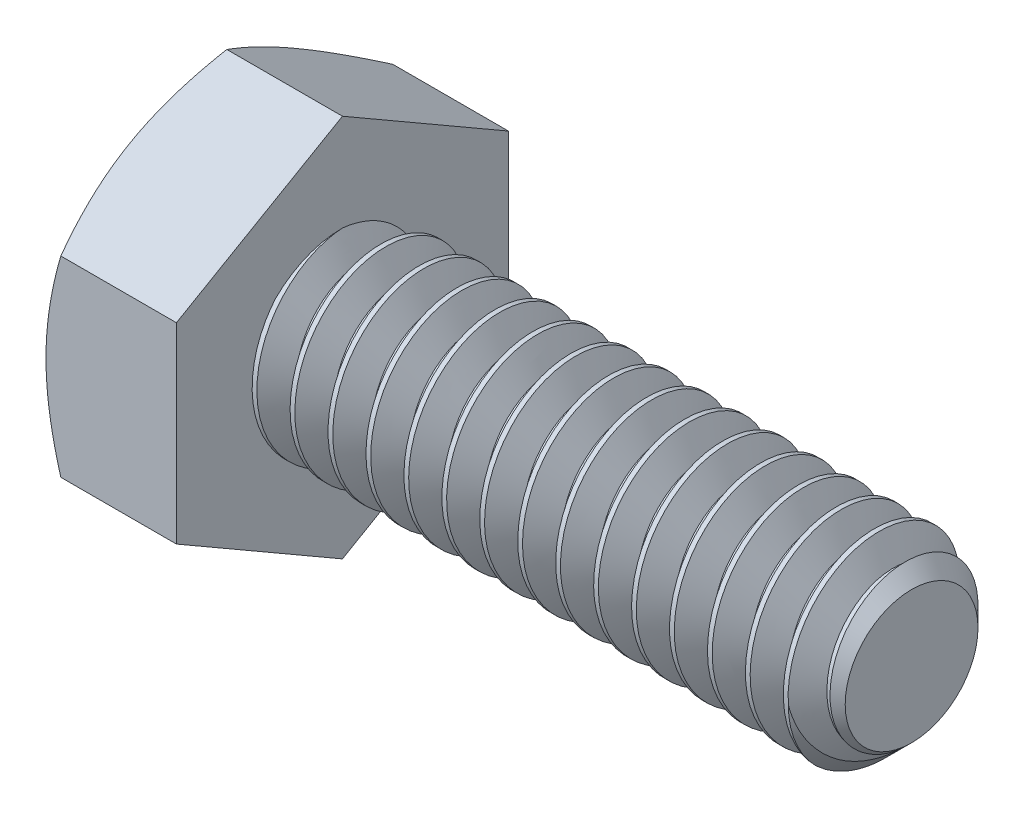
SolidWorks part; units mm, degrees
ref_plane "Front Plane" through (0, 0, 0) normal (0, 0, 1) x (1, 0, 0)
ref_plane "Top Plane" through (0, 0, 0) normal (0, 1, 0) x (1, 0, 0)
ref_plane "Right Plane" through (0, 0, 0) normal (1, 0, 0) x (0, 0, -1)
sketch "Sketch1" plane through (0, 0, 0) normal (0, 0, 1) x (1, 0, 0)
  line L0 (-11.7078, 0) -> (11.7078, 0) construction
  line L1 (11.7078, 3.175) -> (11.7078, -3.175) construction
  line L2 (-7.3422, 5.5562) -> (-7.3422, -5.5562) construction
  line L3 (-11.7078, 5.5562) -> (-11.7078, -5.5562) construction
  point P9 (-7.3422, 0)
  point P10 (7.2628, -3.175)
  dimension "Screw Dia" = 6.35
  dimension "Hex" = 11.1125
  dimension "Head Ht" = 4.3656
  dimension "Screw Lenght" = 19.05
  dimension "D1" = 4.445
ref_plane "Plane2" through (11.7078, 0, 0) normal (1, 0, 0) x (0, 0, -1)
sketch "Sketch5" plane through (11.7078, 0, 0) normal (1, 0, 0) x (0, 0, -1)
  circle A0 centre (0, 0) radius 3.175
extrude "Boss-Extrude3" add sketch "Sketch5" against normal up to vertex (19.05 mm away) up to point (-7.3422, 0, 0)
sketch "Sketch9" plane through (11.7078, 0, 0) normal (1, 0, 0) x (0, 0, -1)
  circle A1 centre (0, 0) radius 3.175
  circle A2 centre (0, 0) radius 3.175
  dimension "D1" = 0
curve "Helix/Spiral1" pitch 1.27 height 20.32 turns 16 parameters "Pitch"=1.27
chamfer "Chamfer1" distance 0.9525 angle 45 1 edges at (11.7078, 0, -3.175)
sketch "Sketch10" plane through (0, 0, 0) normal (0, 0, 1) x (1, 0, 0)
  line L0 (11.7078, 3.175) -> (12.1841, 2.3501)
  line L1 (12.1841, 2.3501) -> (12.3428, 2.3501)
  line L2 (12.3428, 2.3501) -> (12.8191, 3.175)
  line L3 (11.7078, 3.175) -> (12.8191, 3.175)
  line L4 (12.2634, 3.175) -> (12.2634, 2.3501) construction
  line L5 (11.9459, 2.7626) -> (12.5809, 2.7626) construction
  dimension "D1" = 60
  dimension "D2" = 0.1588
  dimension "D3" = 0.635
sweep "Cut-Sweep1" cut profiles "Sketch10" path "Helix/Spiral1"
sketch "Sketch11" plane through (0, 0, 0) normal (0, 0, 1) x (1, 0, 0)
  line L0 (-7.3422, 3.175) -> (-7.3422, 0)
  line L1 (-7.3422, 0) -> (-16.8672, 0)
  line L3 (-16.8672, 0) -> (-20.0422, 3.175)
  line L4 (-7.3422, 3.175) -> (-20.0422, 3.175)
  dimension "D1" = 45
  dimension "MIn Thread" = 31.75
revolve "Revolve1" [suppressed] add sketch "Sketch11" angle 360 about L1
sketch "Sketch6" plane through (-7.3422, 0, 0) normal (-1, 0, 0) x (0, 0, 1)
  line L0 (0, 5.5562) -> (0, -5.5562) construction
  line L1 (5.5562, 3.2079) -> (0, 6.4158)
  line L2 (0, 6.4158) -> (-5.5563, 3.2079)
  line L3 (-5.5563, 3.2079) -> (-5.5563, -3.2079)
  line L4 (-5.5563, -3.2079) -> (0, -6.4158)
  line L5 (0, -6.4158) -> (5.5563, -3.2079)
  line L6 (5.5563, -3.2079) -> (5.5562, 3.2079)
  circle A0 centre (0, 0) radius 5.5563 construction
extrude "Boss-Extrude4" add sketch "Sketch6" along normal up to vertex (4.3656 mm away) up to point (-11.7078, -5.5562, 0)
sketch "Sketch7" plane through (-11.7078, 0, 0) normal (-1, 0, 0) x (0, 0, 1)
  circle A0 centre (0, 0) radius 5.5563 construction
  circle A1 centre (0, 0) radius 5.5563
sketch "Sketch8" plane through (-11.7078, 0, 0) normal (-1, 0, 0) x (0, 0, 1)
  circle A0 centre (0, 0) radius 5.5563 construction
  circle A1 centre (0, 0) radius 5.5563
extrude "Cut-Extrude3" cut sketch "Sketch8" against normal through all draft 60 flip side to cut
equation "\"D2@Sketch10\" = \"Pitch@Helix/Spiral1\"*.125"
equation "\"D3@Sketch10\" = \"Pitch@Helix/Spiral1\"*.5"
equation "\"D3@Helix/Spiral1\" = \"Screw Lenght@Sketch1\"+\"Pitch@Helix/Spiral1\""
equation "\"D1@Chamfer1\" = \"Pitch@Helix/Spiral1\"*.75"
equation "\"D1@Sketch1\" = \"Pitch@Helix/Spiral1\"*3.5"
